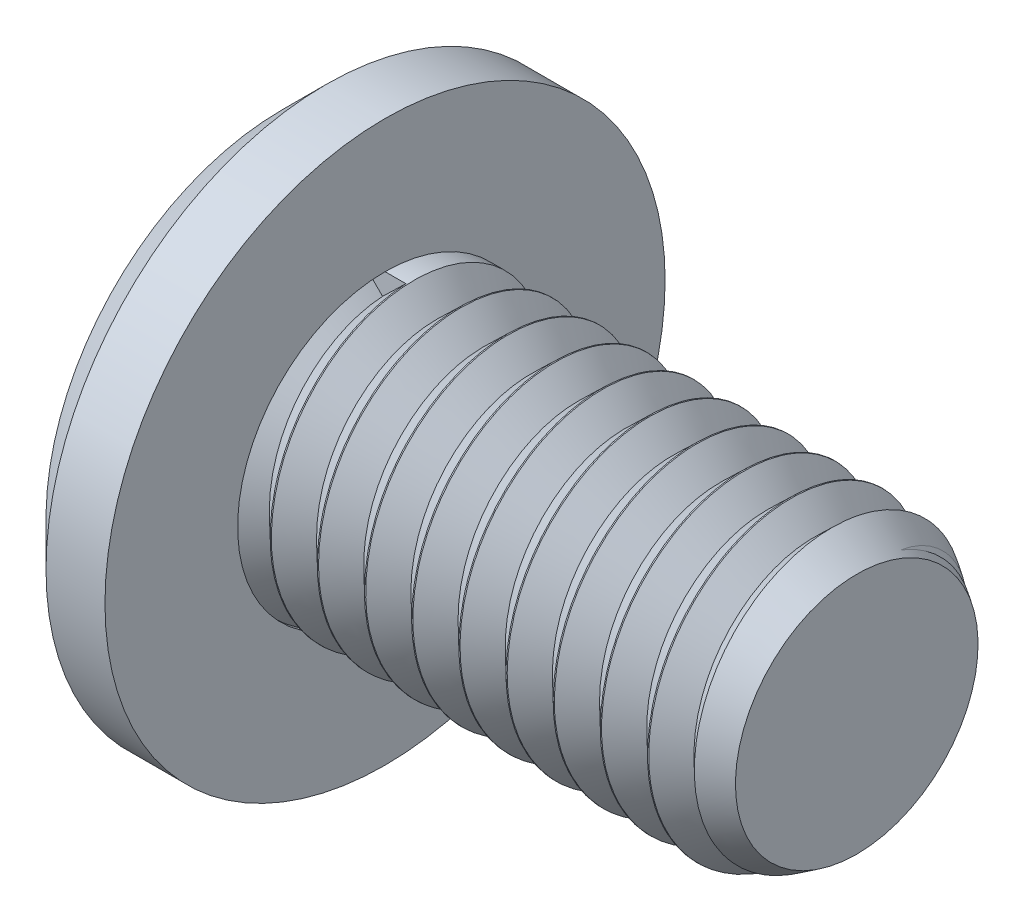
SolidWorks part; units mm, degrees
ref_plane "Front Plane" through (0, 0, 0) normal (0, 0, 1) x (1, 0, 0)
ref_plane "Top Plane" through (0, 0, 0) normal (0, 1, 0) x (1, 0, 0)
ref_plane "Right Plane" through (0, 0, 0) normal (1, 0, 0) x (0, 0, -1)
ref_plane "Plane1" through (5, 0, 0) normal (1, 0, 0) x (0, 0, -1)
sketch "Sketch1" plane through (0, 0, 0) normal (0, 0, 1) x (1, 0, 0)
  line L0 (9.75, 0) -> (9.75, 2.0572)
  line L1 (9.055, 2.5) -> (1.75, 2.5)
  line L2 (1.75, 2.5) -> (1.75, 4.75)
  line L3 (1.75, 4.75) -> (0, 4.75)
  line L4 (0, 0) -> (101.6, 0) construction
  line L7 (9.75, 0) -> (0, 0)
  line L9 (0, 4.75) -> (0, 0)
  line L10 (9.75, 2.0572) -> (9.055, 2.5)
  line L14 (0, 4.75) -> (0, 0) construction
  dimension "D1" = 8
  dimension "D2" = 2.5
  dimension "D3" = 1.75
  dimension "D4" = 122.5
  dimension "D5" = 2.0572
  dimension "D6" = 2.25
revolve "Revolve1" add sketch "Sketch1" angle 360 about L4
sketch "Sketch2" plane through (1.75, 0, 0) normal (1, 0, 0) x (0, 0, -1)
  circle A0 centre (0, 0) radius 2.55
  dimension "D1" = 5.1
curve "Helix/Spiral1" pitch 0.8 height 24.8 turns 31
sketch "Sketch4" plane through (0, 0, 0) normal (0, 0, 1) x (1, 0, 0)
  line L0 (26.9044, 2.5) -> (26.1244, 2.5)
  line L1 (26.9044, 2.5) -> (26.5079, 2.1165)
  line L2 (26.5079, 2.1165) -> (26.1244, 2.5)
  dimension "D1" = 0.78
  dimension "D2" = 45
  dimension "D3" = 2.5
sweep "Cut-Sweep2" cut profiles "Sketch4" path "Helix/Spiral1"
sketch "Sketch5" plane through (0, 0, 0) normal (-1, 0, 0) x (0, 0, 1)
  line L1 (1.5, -0.866) -> (1.5, 0.866)
  line L2 (1.5, 0.866) -> (0, 1.7321)
  line L3 (0, 1.7321) -> (-1.5, 0.866)
  line L4 (-1.5, 0.866) -> (-1.5, -0.866)
  line L5 (-1.5, -0.866) -> (0, -1.7321)
  line L6 (0, -1.7321) -> (1.5, -0.866)
  circle A0 centre (0, 0) radius 1.5 construction
  dimension "D1" = 3
extrude "Cut-Extrude1" cut sketch "Sketch5" against normal blind 1
chamfer "Chamfer1" distance 0.75 angle 45 1 edges at (0, -4.75, 0)
